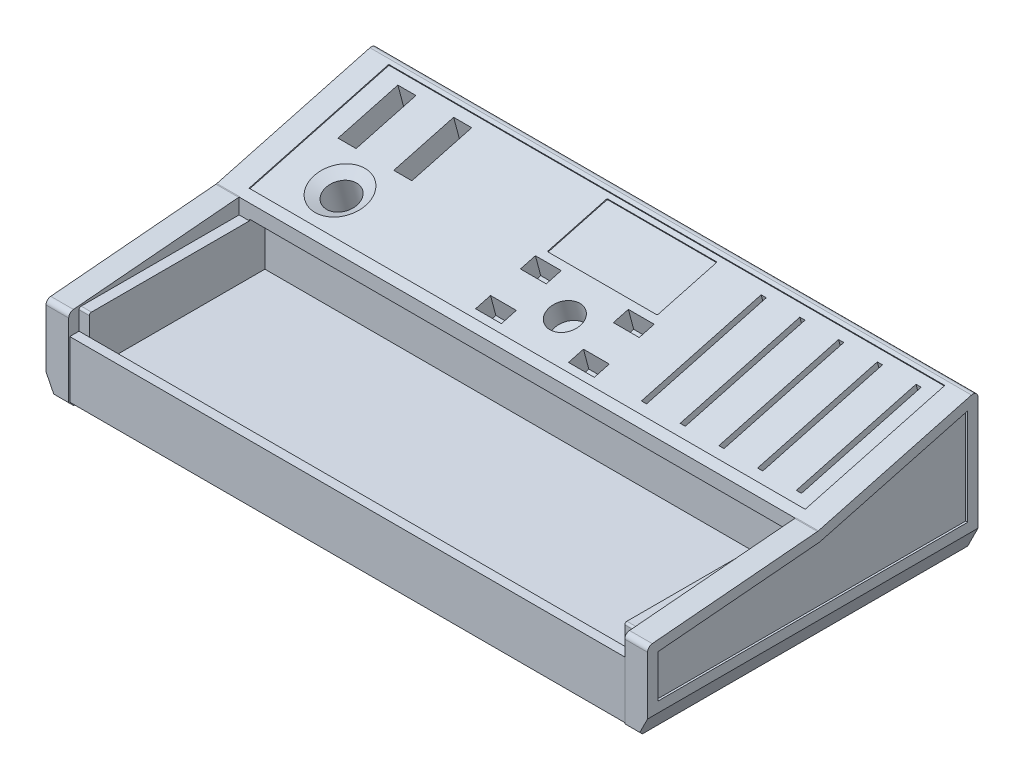
SolidWorks part; units mm, degrees
material "Balsa"
ref_plane "Front Plane" through (0, 0, 0) normal (0, 0, 1) x (1, 0, 0)
ref_plane "Top Plane" through (0, 0, 0) normal (0, 1, 0) x (1, 0, 0)
ref_plane "Right Plane" through (0, 0, 0) normal (1, 0, 0) x (0, 0, -1)
sketch "Sketch1" plane through (0, 0, 0) normal (0, 1, 0) x (1, 0, 0)
  line L1 (-291.25, -82.5) -> (291.25, -82.5)
  line L2 (-291.25, -82.5) -> (-291.25, 82.5)
  line L3 (-291.25, 82.5) -> (291.25, 82.5)
  line L4 (291.25, -82.5) -> (291.25, 82.5)
  line L5 (-291.25, -82.5) -> (291.25, 82.5) construction
  line L6 (-291.25, 82.5) -> (291.25, -82.5) construction
  point P0 (0, 0)
  dimension "D1" = 582.5
  dimension "D2" = 165
extrude "Boss-Extrude1" add sketch "Sketch1" along normal blind 95
sketch "Sketch2" plane through (0, 95, 0) normal (0, 1, 0) x (1, 0, 0)
  line L0 (291.25, 82.5) -> (-291.25, 82.5) construction
  line L1 (-259.25, 82.5) -> (259.25, 82.5)
  line L2 (-259.25, 82.5) -> (-259.25, -72.5)
  line L3 (-259.25, -72.5) -> (259.25, -72.5)
  line L4 (259.25, 82.5) -> (259.25, -72.5)
  line L5 (-291.25, 82.5) -> (-291.25, -82.5) construction
  line L6 (291.25, -82.5) -> (291.25, 82.5) construction
  line L7 (-291.25, -82.5) -> (291.25, -82.5) construction
  dimension "D1" = 32
  dimension "D2" = 32
  dimension "D3" = 10
extrude "Cut-Extrude1" cut sketch "Sketch2" against normal blind 63
sketch "Sketch3" plane through (0, 95, 0) normal (0, 1, 0) x (1, 0, 0)
  line L0 (-291.25, -82.5) -> (291.25, -82.5) construction
  line L1 (-269.25, -72.5) -> (269.25, -72.5)
  line L2 (-269.25, -72.5) -> (-269.25, -82.5)
  line L3 (-269.25, -82.5) -> (269.25, -82.5)
  line L4 (269.25, -72.5) -> (269.25, -82.5)
  line L5 (-259.25, 82.5) -> (-259.25, -72.5) construction
  line L6 (259.25, -72.5) -> (259.25, 82.5) construction
  dimension "D1" = 10
  dimension "D2" = 10
  dimension "D3" = 10
extrude "Cut-Extrude2" cut sketch "Sketch3" against normal offset from surface (35 mm away) 60 up to face at (0, 0, 0)
sketch "Sketch4" plane through (0, 95, 0) normal (0, 1, 0) x (1, 0, 0)
  line L0 (-259.25, 82.5) -> (-291.25, 82.5) construction
  line L1 (-259.25, -72.5) -> (-269.25, -72.5)
  line L2 (-259.25, -72.5) -> (-259.25, 82.5)
  line L3 (-259.25, 82.5) -> (-269.25, 82.5)
  line L4 (-269.25, -72.5) -> (-269.25, 82.5)
  line L5 (291.25, 82.5) -> (259.25, 82.5) construction
  line L6 (259.25, -72.5) -> (269.25, -72.5)
  line L7 (259.25, -72.5) -> (259.25, 82.5)
  line L8 (259.25, 82.5) -> (269.25, 82.5)
  line L9 (269.25, -72.5) -> (269.25, 82.5)
extrude "Cut-Extrude3" cut sketch "Sketch4" against normal offset from surface (15 mm away) 20 up to face at (0, 60, 75.8333)
sketch "Sketch6" plane through (291.25, 0, 0) normal (1, 0, 0) x (0, 0, -1)
  line L0 (-82.5, 95) -> (-82.5, 80.5644)
  line L1 (-82.5, 95) -> (-82.5, 0) construction
  line L2 (-82.5, 80.5644) -> (82.5, 95)
  line L3 (82.5, 95) -> (-82.5, 95)
  dimension "D1" = 5
extrude "Cut-Extrude4" cut sketch "Sketch6" against normal through all
sketch "Sketch7" plane through (-291.25, 0, 0) normal (-1, 0, 0) x (0, 0, 1)
  line L0 (-82.5, 95) -> (-237.5, 136.5321)
  line L1 (-237.5, 136.5321) -> (-237.5, 0)
  line L2 (-237.5, 0) -> (-82.5, 0)
  line L3 (82.5, 80.5644) -> (82.5, 0) construction
  line L4 (-82.5, 95) -> (-82.5, 0) construction
  line L5 (-82.5, 95) -> (-82.5, 0)
  dimension "D1" = 320
  dimension "D2" = 105
extrude "Boss-Extrude2" add sketch "Sketch7" against normal through all
sketch "Sketch8" plane through (0, 0, -82.5) normal (0, 0, 1) x (1, 0, 0)
  line L0 (269.25, 95) -> (-269.25, 95) construction
  line L1 (-259.25, 32) -> (259.25, 32)
  line L2 (-259.25, 32) -> (-259.25, 81.5)
  line L3 (-259.25, 81.5) -> (259.25, 81.5)
  line L4 (259.25, 32) -> (259.25, 81.5)
  dimension "D1" = 13.5
extrude "Cut-Extrude5" cut sketch "Sketch8" against normal blind 15
sketch "Sketch9" plane through (0, 0, 82.5) normal (0, 0, 1) x (1, 0, 0)
  line L0 (-291.25, 20) -> (-281.25, 0)
  line L1 (-291.25, 80.5644) -> (-291.25, 0) construction
  line L2 (-291.25, 0) -> (291.25, 0) construction
  line L3 (-281.25, 0) -> (-291.25, 0)
  line L4 (-291.25, 0) -> (-291.25, 20)
  line L5 (281.25, 0) -> (291.25, 20)
  line L6 (291.25, 80.5644) -> (291.25, 0) construction
  line L7 (291.25, 20) -> (291.25, 0)
  line L8 (291.25, 0) -> (281.25, 0)
  dimension "D1" = 20
  dimension "D2" = 10
extrude "Cut-Extrude6" cut sketch "Sketch9" against normal through all
sketch "Sketch11" plane through (0, 0, 82.5) normal (0, 0, 1) x (1, 0, 0)
  line L0 (-269.25, 60) -> (-269.25, 0)
  line L1 (-281.25, 0) -> (281.25, 0) construction
  line L2 (-269.25, 0) -> (269.25, 0)
  line L3 (269.25, 0) -> (269.25, 60)
  line L4 (269.25, 60) -> (-269.25, 60)
extrude "Cut-Extrude7" cut sketch "Sketch11" against normal blind 1
fillet "Fillet1" radius 5 5 edges at (280.25, 95, -82.5) (-280.25, 95, -82.5) (0, 136.5321, -237.5) (280.25, 80.5644, 82.5) (-280.25, 80.5644, 82.5)
fillet "Fillet2" radius 2 2 edges at (264.25, 80, 72.5) (-264.25, 80, 72.5)
sketch "Sketch12" plane through (0, 0, 0) normal (0, -1, 0) x (1, 0, 0)
  line L0 (281.25, -237.5) -> (-281.25, -237.5) construction
  line L1 (-269.25, 81.5) -> (269.25, 81.5)
  line L2 (-269.25, 81.5) -> (-269.25, -237.5)
  line L3 (-269.25, -237.5) -> (269.25, -237.5)
  line L4 (269.25, 81.5) -> (269.25, -237.5)
extrude "Cut-Extrude8" [suppressed] cut sketch "Sketch12" against normal blind 1
chamfer "Chamfer1" distance 5 angle 45 1 edges at (0, 0, 81.5)
chamfer "Chamfer2" distance 5 angle 45 2 edges at (-275.25, 0, 82.5) (275.25, 0, 82.5)
sketch "Sketch13" plane through (-291.25, 0, 0) normal (-1, 0, 0) x (0, 0, 1)
  line L10 (-85.5107, 85.454) -> (-227.5, 123.4999)
  line L11 (-227.5, 123.4999) -> (-227.5, 30)
  line L12 (-227.5, 30) -> (72.5, 30)
  line L13 (72.5, 30) -> (72.5, 71.4011)
  line L14 (72.5, 71.4011) -> (-82.9358, 84.9999)
  line L15 (-85.5107, 85.454) -> (-227.5, 123.4999)
  line L16 (-227.5, 123.4999) -> (-227.5, 30)
  line L17 (-227.5, 30) -> (72.5, 30)
  line L18 (72.5, 30) -> (72.5, 71.4011)
  line L19 (72.5, 71.4011) -> (-82.9358, 84.9999)
  arc A6 (-85.5107, 85.454) -> (-82.9358, 84.9999) centre (-81.6284, 99.9428) ccw
  arc A7 (-85.5107, 85.454) -> (-82.9358, 84.9999) centre (-81.6284, 99.9428) ccw
  dimension "D1" = 10
extrude "Cut-Extrude9" cut sketch "Sketch13" against normal blind 2
mirror "Mirror1" about plane through (0, 0, 0) normal (1, 0, 0) of "Cut-Extrude9"
sketch "Sketch14" plane through (0, 68.0112, 18.2235) normal (0, 0.9659, 0.2588) x (1, 0, 0)
  line L0 (-269.25, 103.8459) -> (-269.25, -54.3252) construction
  line L1 (-269.25, 114.2767) -> (269.25, 114.2767)
  line L2 (-269.25, 114.2767) -> (-269.25, 254.2767)
  line L3 (-269.25, 254.2767) -> (269.25, 254.2767)
  line L4 (269.25, 114.2767) -> (269.25, 254.2767)
  line L5 (269.25, -54.3252) -> (269.25, 103.8459) construction
  line L7 (269.25, 104.2767) -> (-269.25, 104.2767) construction
  line L9 (-161.25, 114.2767) -> (-161.25, 254.2767)
  line L10 (161.25, 114.2767) -> (161.25, 254.2767)
  line L11 (-161.25, 184.2767) -> (161.25, 184.2767) construction
  line L12 (-53.25, 254.2767) -> (-53.25, 114.2767)
  line L14 (53.25, 254.2767) -> (53.25, 114.2767)
  dimension "D1" = 10
  dimension "D2" = 140
  dimension "D3" = 108
  dimension "D4" = 108
  dimension "D5" = 108
  dimension "D6" = 108
sketch "Sketch23" plane through (0, 68.0112, 18.2235) normal (0, 0.9659, 0.2588) x (1, 0, 0)
  line L1 (-269.25, 254.2767) -> (269.25, 254.2767)
  line L2 (-269.25, 254.2767) -> (-269.25, 114.2767)
  line L3 (-269.25, 114.2767) -> (269.25, 114.2767)
  line L4 (269.25, 254.2767) -> (269.25, 114.2767)
extrude "Cut-Extrude18" cut sketch "Sketch23" against normal mid plane 2
sketch "Sketch16" plane through (0, 67.0453, 17.9647) normal (0, 0.9659, 0.2588) x (1, 0, 0)
  line L1 (-269.25, 114.2767) -> (269.25, 114.2767) construction
  line L2 (-269.25, 254.2767) -> (269.25, 254.2767) construction
  line L3 (-269.25, 184.2767) -> (-215.25, 184.2767) construction
  line L4 (-269.25, 114.2767) -> (-269.25, 254.2767) construction
  line L5 (-215.25, 184.2767) -> (-161.25, 184.2767) construction
  line L6 (-242.25, 244.2767) -> (-242.25, 254.2767) construction
  line L7 (-251, 244.2767) -> (-233.5, 244.2767)
  line L8 (-251, 244.2767) -> (-251, 184.2767)
  line L9 (-251, 184.2767) -> (-233.5, 184.2767)
  line L10 (-233.5, 244.2767) -> (-233.5, 184.2767)
  line L11 (-197, 244.2767) -> (-179.5, 244.2767)
  line L12 (-197, 244.2767) -> (-197, 184.2767)
  line L13 (-197, 184.2767) -> (-179.5, 184.2767)
  line L14 (-179.5, 244.2767) -> (-179.5, 184.2767)
  line L15 (-215.25, 124.2767) -> (-215.25, 114.2767) construction
  circle A0 centre (-215.25, 149.2767) radius 25 construction
  circle A1 centre (-215.25, 149.2767) radius 15
  point P20 (-188.25, 184.2767)
  point P21 (-188.25, 244.2767)
  point P22 (-242.25, 184.2767)
  point P23 (-242.25, 244.2767)
  dimension "D3" = 50
  dimension "D6" = 30
  dimension "D1" = 17.5
  dimension "D2" = 17.5
  dimension "D4" = 60
  dimension "D5" = 10
extrude "Cut-Extrude11" cut sketch "Sketch16" against normal blind 60
chamfer "Chamfer4" distance 10 angle 30 1 edges at (-215.25, 101.7986, -111.7366) first distance on face at (-242.25, 122.5042, -189.0107)
sketch "Sketch17" plane through (0, 9.0897, 2.4356) normal (0, 0.9659, 0.2588) x (1, 0, 0)
  line L0 (-233.5, 244.2767) -> (-251, 244.2767) construction
  line L1 (-251, 177.2767) -> (-233.5, 177.2767)
  line L2 (-251, 177.2767) -> (-251, 251.2767)
  line L3 (-251, 251.2767) -> (-233.5, 251.2767)
  line L4 (-233.5, 177.2767) -> (-233.5, 251.2767)
  line L5 (-197, 177.2767) -> (-179.5, 177.2767)
  line L6 (-197, 177.2767) -> (-197, 251.2767)
  line L7 (-197, 251.2767) -> (-179.5, 251.2767)
  line L8 (-179.5, 177.2767) -> (-179.5, 251.2767)
  line L9 (-251, 184.2767) -> (-233.5, 184.2767) construction
  line L10 (-251, 244.2767) -> (-251, 184.2767) construction
  line L11 (-233.5, 184.2767) -> (-233.5, 244.2767) construction
  line L12 (-197, 244.2767) -> (-197, 184.2767) construction
  point P12 (-242.25, 184.2767)
  dimension "D1" = 7
  dimension "D2" = 7
extrude "Cut-Extrude12" [suppressed] cut sketch "Sketch17" along normal offset from surface (58 mm away) 2 up to face at (-215.25, 99.2105, -102.0773)
sketch "Sketch18" plane through (0, 67.0453, 17.9647) normal (0, 0.9659, 0.2588) x (1, 0, 0)
  line L0 (-53.25, 254.2767) -> (-53.25, 114.2767) construction
  line L1 (-53.25, 249.2767) -> (53.25, 249.2767)
  line L2 (-53.25, 249.2767) -> (-53.25, 189.3704)
  line L3 (-53.25, 189.3704) -> (53.25, 189.3704)
  line L4 (53.25, 249.2767) -> (53.25, 189.3704)
  line L6 (-269.25, 254.2767) -> (269.25, 254.2767) construction
  dimension "D2" = 106.5
  dimension "D1" = 5
  dimension "D3" = 59.9063
extrude "Cut-Extrude13" cut sketch "Sketch18" against normal blind 1
fillet "Fillet3" radius 1 4 edges at (53.25, 115.575, -165.0825) (53.25, 131.0799, -222.9475) (-53.25, 131.0799, -222.9475) (-53.25, 115.575, -165.0825)
sketch "Sketch19" plane through (0, 67.0453, 17.9647) normal (0, 0.9659, 0.2588) x (1, 0, 0)
  line L0 (0, 189.3704) -> (0, 114.2767) construction
  line L2 (-269.25, 114.2767) -> (269.25, 114.2767) construction
  line L3 (-52.25, 189.3704) -> (52.25, 189.3704) construction
  circle A0 centre (0, 151.8236) radius 25 construction
  circle A1 centre (0, 151.8236) radius 15
  dimension "D1" = 50
  dimension "D2" = 30
extrude "Cut-Extrude14" cut sketch "Sketch19" against normal blind 20
sketch "Sketch20" plane through (0, 47.7268, 12.7883) normal (0, 0.9659, 0.2588) x (1, 0, 0)
  circle A0 centre (0, 151.8236) radius 20
  dimension "D1" = 40
extrude "Cut-Extrude15" [suppressed] cut sketch "Sketch20" against normal blind 20
sketch "Sketch21" plane through (0, 67.0453, 17.9647) normal (0, 0.9659, 0.2588) x (1, 0, 0)
  line L0 (-45, 174.3236) -> (0, 151.8236) construction
  line L1 (-57.5, 181.8236) -> (-32.5, 181.8236)
  line L2 (-57.5, 181.8236) -> (-57.5, 166.8236)
  line L3 (-57.5, 166.8236) -> (-32.5, 166.8236)
  line L4 (-32.5, 181.8236) -> (-32.5, 166.8236)
  line L5 (-57.5, 181.8236) -> (-32.5, 166.8236) construction
  line L6 (-57.5, 166.8236) -> (-32.5, 181.8236) construction
  line L7 (-57.5, 136.8236) -> (-32.5, 136.8236)
  line L8 (-57.5, 136.8236) -> (-57.5, 121.8236)
  line L9 (-57.5, 121.8236) -> (-32.5, 121.8236)
  line L10 (-32.5, 136.8236) -> (-32.5, 121.8236)
  line L11 (-57.5, 136.8236) -> (-32.5, 121.8236) construction
  line L12 (-57.5, 121.8236) -> (-32.5, 136.8236) construction
  line L13 (32.5, 136.8236) -> (57.5, 136.8236)
  line L14 (32.5, 136.8236) -> (32.5, 121.8236)
  line L15 (32.5, 121.8236) -> (57.5, 121.8236)
  line L16 (57.5, 136.8236) -> (57.5, 121.8236)
  line L17 (32.5, 136.8236) -> (57.5, 121.8236) construction
  line L18 (32.5, 121.8236) -> (57.5, 136.8236) construction
  line L19 (32.5, 181.8236) -> (57.5, 181.8236)
  line L20 (32.5, 181.8236) -> (32.5, 166.8236)
  line L21 (32.5, 166.8236) -> (57.5, 166.8236)
  line L22 (57.5, 181.8236) -> (57.5, 166.8236)
  line L23 (32.5, 181.8236) -> (57.5, 166.8236) construction
  line L24 (32.5, 166.8236) -> (57.5, 181.8236) construction
  line L25 (0, 151.8236) -> (-45, 129.3236) construction
  line L27 (45, 129.3236) -> (0, 151.8236) construction
  line L28 (0, 151.8236) -> (45, 174.3236) construction
  point P0 (-45, 174.3236)
  point P5 (-45, 129.3236)
  point P10 (45, 129.3236)
  point P15 (45, 174.3236)
  dimension "D1" = 25
  dimension "D2" = 15
  dimension "D3" = 45
  dimension "D4" = 45
  dimension "D5" = 45
  dimension "D6" = 45
  dimension "D7" = 30
  dimension "D8" = 30
extrude "Cut-Extrude16" cut sketch "Sketch21" against normal blind 20
sketch "Sketch22" plane through (0, 67.0453, 17.9647) normal (0, 0.9659, 0.2588) x (1, 0, 0)
  line L0 (-161.25, 184.2767) -> (161.25, 184.2767) construction
  line L1 (105.75, 244.2767) -> (100.75, 244.2767)
  line L2 (105.75, 244.2767) -> (105.75, 124.2767)
  line L3 (105.75, 124.2767) -> (100.75, 124.2767)
  line L4 (100.75, 244.2767) -> (100.75, 124.2767)
  line L5 (105.75, 244.2767) -> (100.75, 124.2767) construction
  line L6 (105.75, 124.2767) -> (100.75, 244.2767) construction
  line L7 (53.25, 254.2767) -> (53.25, 114.2767) construction
  point P0 (103.25, 184.2767)
  dimension "D1" = 120
  dimension "D2" = 5
  dimension "D3" = 50
extrude "Cut-Extrude17" cut sketch "Sketch22" against normal up to surface (20 mm away) up to face at (-45, 92.845, -155.5953)
pattern_linear "LPattern3" count 5 spacing 37.5 along (1, 0, 0) of "Cut-Extrude17"
fillet "Fillet4" [suppressed] radius 1
fillet "Fillet5" [suppressed] radius 1
equation "\"D3@Sketch18\"=\"D2@Sketch18\"*9/16"
